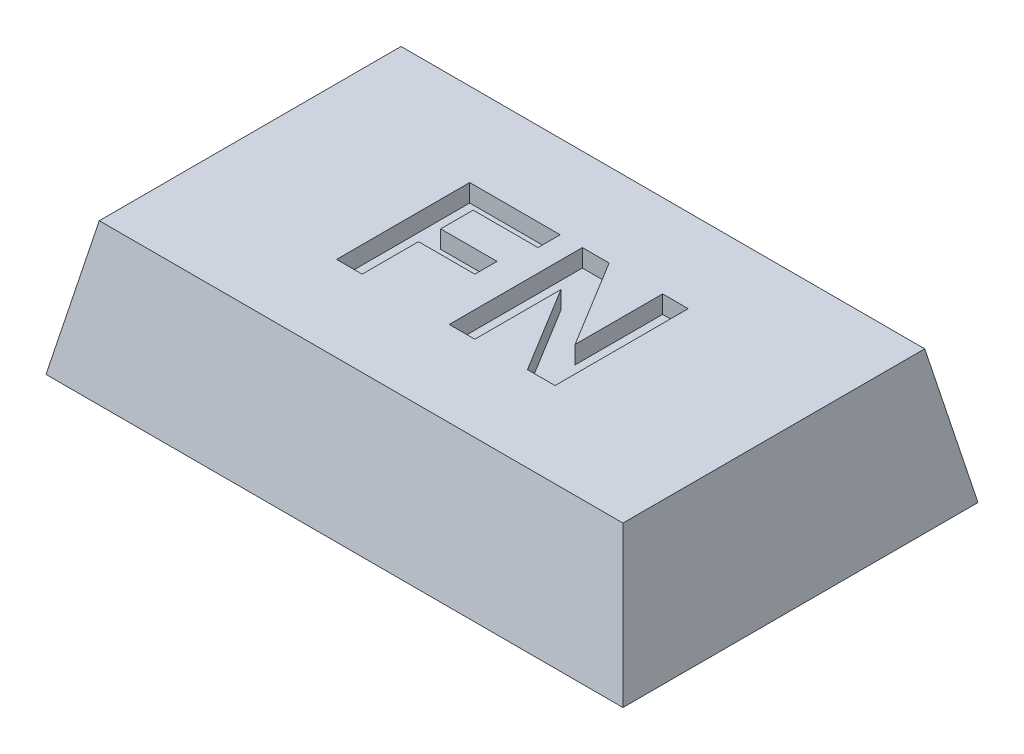
SolidWorks part; units mm, degrees
ref_plane "Front Plane" through (0, 0, 0) normal (0, 0, 1) x (1, 0, 0)
ref_plane "Top Plane" through (0, 0, 0) normal (0, 1, 0) x (1, 0, 0)
ref_plane "Right Plane" through (0, 0, 0) normal (1, 0, 0) x (0, 0, -1)
sketch "Sketch1" plane through (0, 0, 0) normal (0, 1, 0) x (1, 0, 0)
  line L1 (0, 0) -> (13, 0)
  line L2 (0, 0) -> (0, 8)
  line L3 (0, 8) -> (13, 8)
  line L4 (13, 0) -> (13, 8)
  dimension "D1" = 8
  dimension "D2" = 13
extrude "Boss-Extrude1" add sketch "Sketch1" along normal blind 3
sketch "Sketch2" plane through (0, 0, 0) normal (0, 0, 1) x (1, 0, 0)
  line L0 (0, 0) -> (0.6, 3)
  line L1 (0, 3) -> (13, 3) construction
  line L2 (0.6, 3) -> (0, 3)
  line L3 (0, 3) -> (0, 0)
  line L4 (13, 0) -> (12.4, 3)
  line L5 (12.4, 3) -> (13, 3)
  line L6 (13, 3) -> (13, 0)
  dimension "D1" = 0.6
  dimension "D2" = 0.6
extrude "Cut-Extrude1" cut sketch "Sketch2" against normal through all both and the other way through all
sketch "Sketch3" plane through (0, 0, 0) normal (1, 0, 0) x (0, 0, -1)
  line L0 (0, 0) -> (0.6, 3)
  line L1 (8, 3) -> (0, 3) construction
  line L2 (0.6, 3) -> (0, 3)
  line L3 (0, 3) -> (0, 0)
  line L4 (8, 3) -> (7.4, 3)
  line L5 (7.4, 3) -> (8, 0)
  line L6 (8, 3) -> (8, 0)
  dimension "D1" = 0.6
  dimension "D2" = 0.6
extrude "Cut-Extrude2" cut sketch "Sketch3" along normal through all both and the other way through all
sketch "Sketch4" plane through (0, 0, 0) normal (0, -1, 0) x (1, 0, 0)
  line L1 (6.5, 0) -> (6.5, -8) construction
  line L2 (13, -8) -> (0, -8) construction
  line L3 (0, 0) -> (13, 0) construction
  circle A0 centre (6.5, -3.75) radius 1.8
  dimension "D1" = 3.6
  dimension "D2" = 0
  dimension "D3" = 3.75
extrude "Cut-Extrude3" cut sketch "Sketch4" against normal blind 0.8
sketch "Sketch5" plane through (0, 0, 0) normal (0, -1, 0) x (1, 0, 0)
  line L5 (0, 0) -> (13, 0) construction
  line L6 (2.5, -8) -> (10.5, -8)
  line L7 (2.5, -8) -> (2.5, -6.9)
  line L8 (2.5, -6.9) -> (10.5, -6.9)
  line L9 (10.5, -8) -> (10.5, -6.9)
  point P2 (6.5, 0)
  dimension "D1" = 1.1
  dimension "D2" = 4
  dimension "D3" = 4
extrude "Boss-Extrude2" add sketch "Sketch5" along normal blind 2
fillet "Fillet1" radius 4 2 edges at (10.5, -2, -7.45) (2.5, -2, -7.45)
sketch "Sketch6" plane through (0, 3, 0) normal (0, 1, 0) x (1, 0, 0)
  text T0 "FN" font "Arial" height 3
extrude "Cut-Extrude4" cut sketch "Sketch6" against normal blind 0.4
